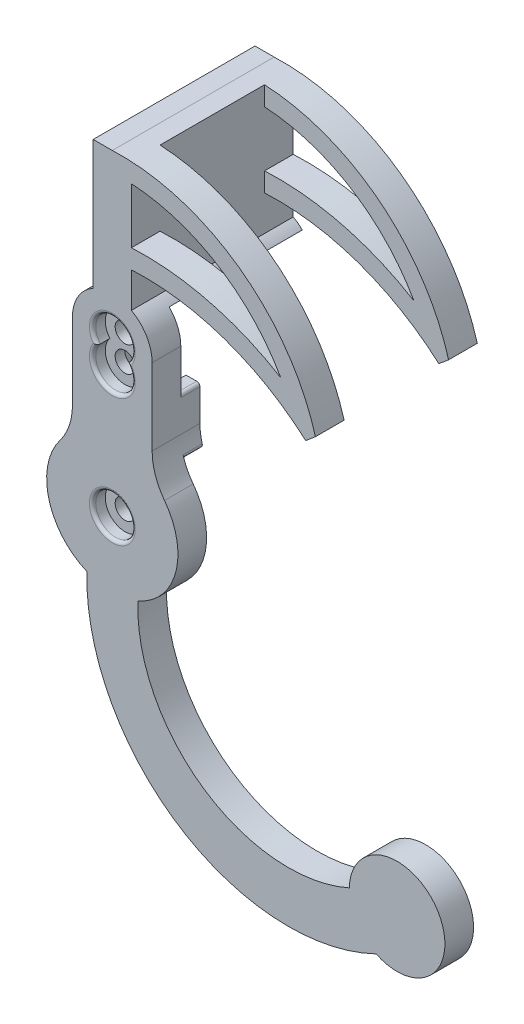
SolidWorks part; units mm, degrees
material "PLA"
ref_plane "Front Plane" through (0, 0, 0) normal (0, 0, 1) x (1, 0, 0)
ref_plane "Top Plane" through (0, 0, 0) normal (0, 1, 0) x (1, 0, 0)
ref_plane "Right Plane" through (0, 0, 0) normal (1, 0, 0) x (0, 0, -1)
sketch "Sketch1" plane through (0, 0, 0) normal (0, 0, 1) x (1, 0, 0)
  line L0 (-15.8075, -15.8075) -> (15.8075, 15.8075) construction
  line L1 (-15.8075, 15.8075) -> (15.8075, -15.8075) construction
  line L2 (0, 0) -> (0, 22.3552) construction
  line L3 (-3.5028, 12) -> (-3.35, 24)
  line L4 (-6.2528, 12) -> (-6.2528, 24)
  line L5 (6.2528, 12) -> (6.2528, 24)
  line L6 (3.5028, 12) -> (3.35, 24)
  line L9 (0.65, -3.8962) -> (0.65, -7.1706)
  line L10 (3.15, 12) -> (3.15, 24)
  line L11 (-3.15, 24) -> (-3.15, 12)
  line L12 (-0.65, -7.1706) -> (-0.65, -3.8962)
  line L13 (-0.65, 3.8962) -> (-0.65, 7.6481)
  line L14 (0.65, 7.6481) -> (0.65, 3.8962)
  line L15 (0.65, -3.8962) -> (0.65, -7.1706) construction
  line L16 (3.15, 12) -> (3.15, 24) construction
  line L17 (-3.15, 24) -> (-3.15, 12) construction
  line L18 (-0.65, -7.1706) -> (-0.65, -3.8962) construction
  line L19 (-0.65, 3.8962) -> (-0.65, 7.6481) construction
  line L20 (0.65, 7.6481) -> (0.65, 3.8962) construction
  circle A0 centre (0, 0) radius 22.3552 construction
  circle A1 centre (0, 20) radius 1.55
  circle A2 centre (0, 24) radius 1.55
  arc A3 (0.7949, 10.2721) -> (-0.7949, 10.2721) centre (0, 0) ccw
  circle A4 centre (-15.7528, 12) radius 12.25 construction
  arc A5 (-3.7402, 9.5999) -> (-3.5028, 12) centre (-15.7528, 12) ccw
  arc A6 (3.35, 24) -> (-3.35, 24) centre (0, 24) ccw
  circle A7 centre (-15.7528, 12) radius 9.5 construction
  arc A9 (-6.2528, 12) -> (-8.1957, 6.2432) centre (-15.7528, 12) cw
  arc A11 (-6.2528, 24) -> (6.2528, 24) centre (0, 24) cw
  arc A12 (0.65, -7.1706) -> (5.7275, 4.363) centre (0, 0) ccw
  arc A13 (3.15, 12) -> (5.7275, 4.363) centre (15.7528, 12) ccw
  arc A14 (3.15, 24) -> (-3.15, 24) centre (0, 24) ccw
  arc A15 (-5.7275, 4.363) -> (-3.15, 12) centre (-15.7528, 12) ccw
  arc A16 (-5.7275, 4.363) -> (-0.65, -7.1706) centre (0, 0) ccw
  arc A17 (-0.65, 3.8962) -> (-0.65, -3.8962) centre (0, 0) ccw
  arc A18 (0.65, 7.6481) -> (-0.65, 7.6481) centre (0, 9) ccw
  arc A19 (0.65, -3.8962) -> (0.65, 3.8962) centre (0, 0) ccw
  arc A20 (0.65, -7.1706) -> (5.7275, 4.363) centre (0, 0) ccw construction
  arc A21 (3.15, 12) -> (5.7275, 4.363) centre (15.7528, 12) ccw construction
  arc A22 (3.15, 24) -> (-3.15, 24) centre (0, 24) ccw construction
  arc A23 (-5.7275, 4.363) -> (-3.15, 12) centre (-15.7528, 12) ccw construction
  arc A24 (-5.7275, 4.363) -> (-0.65, -7.1706) centre (0, 0) ccw construction
  arc A25 (-0.65, 3.8962) -> (-0.65, -3.8962) centre (0, 0) ccw construction
  arc A26 (0.65, 7.6481) -> (-0.65, 7.6481) centre (0, 9) ccw construction
  arc A27 (0.65, -3.8962) -> (0.65, 3.8962) centre (0, 0) ccw construction
  arc A29 (-8.1957, 6.2432) -> (8.1957, 6.2432) centre (0, 0) ccw
  circle A30 centre (0, 0) radius 7.7902
  arc A31 (-3.7402, 9.5999) -> (-5.1734, 5.8243) centre (22.9017, -2.673) ccw
  arc A32 (3.7402, 9.5999) -> (5.1734, 5.8243) centre (-22.9017, -2.673) cw
  arc A33 (3.7402, 9.5999) -> (3.5028, 12) centre (15.7528, 12) cw
  arc A34 (6.2528, 12) -> (8.1957, 6.2432) centre (15.7528, 12) ccw
  dimension "D1" = 3.1
  dimension "D2" = 3.1
  dimension "D6" = 19
  dimension "D8" = 24.5
  dimension "D9" = 15.5803
  dimension "D3" = 4
  dimension "D4" = 20
  dimension "D5" = 45
  dimension "D7" = 0
extrude "Boss-Extrude1" add sketch "Sketch1" along normal blind 3.5 contours A2 | A1 | A9 A29 A34 L5 A11 L4 region at (0, 20, 0) region at (0, 24, 0)
extrude "Boss-Extrude2" add sketch "Sketch1<6>" against normal blind 1 contours A9 A29 A34 L5 A11 L4 A33 A32 A30 A31 A5 L3 A6 L6 region at (-5.7979, 18, 0)
sketch "Sketch1<6>" plane through (0, 0, 0) normal (0, 0, 1) x (1, 0, 0) same geometry as "Sketch1"
sketch "Sketch2" plane through (0, 0, -1) normal (0, 0, -1) x (-1, 0, 0)
  line L0 (3.5832, 17.4665) -> (3.6529, 11.9938)
  line L1 (0, 0) -> (0, 24) construction
  line L2 (6.2528, 12) -> (6.2528, 24)
  line L3 (-6.2528, 24) -> (-6.2528, 12)
  line L4 (6.2528, 12) -> (6.2528, 24)
  line L5 (-6.2528, 24) -> (-6.2528, 12)
  line L6 (3.5028, 12) -> (3.35, 24)
  line L7 (-3.35, 24) -> (-3.5028, 12)
  line L8 (3.5028, 12) -> (3.35, 24) construction
  line L9 (-3.35, 24) -> (-3.5028, 12) construction
  line L10 (6.2528, 17.5004) -> (3.5832, 17.4665)
  line L11 (4.2882, 8.1307) -> (6.7516, 8.9621)
  line L12 (-3.5832, 17.4665) -> (-3.6529, 11.9938)
  line L13 (-6.2528, 17.5004) -> (-3.5832, 17.4665)
  line L14 (-4.2882, 8.1307) -> (-6.7516, 8.9621)
  circle A0 centre (15.7528, 12) radius 12.0999 construction
  arc A1 (4.2882, 8.1307) -> (3.6529, 11.9938) centre (15.7528, 12) cw
  arc A2 (-4.2882, 8.1307) -> (-3.6529, 11.9938) centre (-15.7528, 12) ccw
  arc A4 (6.2528, 12) -> (8.1957, 6.2432) centre (15.7528, 12) ccw
  arc A5 (6.2528, 24) -> (-6.2528, 24) centre (0, 24) ccw
  arc A6 (-8.1957, 6.2432) -> (-6.2528, 12) centre (-15.7528, 12) ccw
  arc A7 (-8.1957, 6.2432) -> (8.1957, 6.2432) centre (0, 0) ccw
  arc A8 (6.2528, 12) -> (8.1957, 6.2432) centre (15.7528, 12) ccw
  arc A9 (6.2528, 24) -> (-6.2528, 24) centre (0, 24) ccw
  arc A10 (-8.1957, 6.2432) -> (-6.2528, 12) centre (-15.7528, 12) ccw
  arc A11 (-8.1957, 6.2432) -> (8.1957, 6.2432) centre (0, 0) ccw
  arc A14 (-3.7402, 9.5999) -> (-3.5028, 12) centre (-15.7528, 12) ccw
  arc A15 (-3.7402, 9.5999) -> (-5.1734, 5.8243) centre (22.9017, -2.673) ccw
  arc A16 (-5.1734, 5.8243) -> (5.1734, 5.8243) centre (0, 0) ccw
  arc A17 (5.1734, 5.8243) -> (3.7402, 9.5999) centre (-22.9017, -2.673) ccw
  arc A18 (3.5028, 12) -> (3.7402, 9.5999) centre (15.7528, 12) ccw
  arc A19 (3.35, 24) -> (-3.35, 24) centre (0, 24) ccw
  arc A20 (-3.7402, 9.5999) -> (-3.5028, 12) centre (-15.7528, 12) ccw construction
  arc A21 (-3.7402, 9.5999) -> (-5.1734, 5.8243) centre (22.9017, -2.673) ccw construction
  arc A22 (-5.1734, 5.8243) -> (5.1734, 5.8243) centre (0, 0) ccw construction
  arc A23 (5.1734, 5.8243) -> (3.7402, 9.5999) centre (-22.9017, -2.673) ccw construction
  arc A24 (3.5028, 12) -> (3.7402, 9.5999) centre (15.7528, 12) ccw construction
  arc A25 (3.35, 24) -> (-3.35, 24) centre (0, 24) ccw construction
  arc M20 (8.1957, 6.2432) -> (6.2528, 12) centre (15.7528, 12) cw
  line M21 (6.2528, 12) -> (6.2528, 24)
  arc M24 (-6.2528, 12) -> (-8.1957, 6.2432) centre (-15.7528, 12) cw
  dimension "D3" = 0.15
  dimension "D4" = 5.5
  dimension "D1" = 0
  dimension "D2" = 0
extrude "Boss-Extrude3" add sketch "Sketch2" along normal blind 3 contours A1 L11 L10 L0 M20 M21 | L14 A2 L12 L13 L5 M24 region at (-4.9977, 13.015, -1) region at (4.9977, 13.015, -1)
sketch "Sketch3" plane through (0, 0, 3.5) normal (0, 0, 1) x (1, 0, 0)
  circle A0 centre (0, 24) radius 1.55 construction
  circle A1 centre (0, 20) radius 1.55 construction
  circle A2 centre (0, 24) radius 1.55
  circle A3 centre (0, 20) radius 1.55
  circle A4 centre (0, 20) radius 3.1
  circle A5 centre (0, 24) radius 3.1
  dimension "D1" = 6.2
  dimension "D2" = 6.2
extrude "Cut-Extrude1" cut sketch "Sketch3" against normal blind 2
sketch "Sketch8" plane through (0, 0, 0) normal (0, 0, -1) x (-1, 0, 0)
  line L0 (3.75, 24) -> (4.4574, 9)
  line L1 (4.4574, 9) -> (7.2239, 3.9848)
  line L2 (0, 24) -> (0, 0) construction
  line L3 (-4.4574, 9) -> (-7.2239, 3.9848)
  line L4 (-3.75, 24) -> (-4.4574, 9)
  circle A0 centre (0, 0) radius 8.25
  circle A1 centre (0, 24) radius 3.75
  arc M7 (-3.5028, 12) -> (-3.7402, 9.5999) centre (-15.7528, 12) cw
  arc M8 (-3.7402, 9.5999) -> (-5.1734, 5.8243) centre (22.9017, -2.673) ccw
  arc M9 (-5.1734, 5.8243) -> (5.1734, 5.8243) centre (0, 0) ccw
  arc M10 (5.1734, 5.8243) -> (3.7402, 9.5999) centre (-22.9017, -2.673) ccw
  arc M11 (3.7402, 9.5999) -> (3.5028, 12) centre (15.7528, 12) cw
  line M12 (3.5028, 12) -> (3.35, 24)
  arc M13 (3.35, 24) -> (-3.35, 24) centre (0, 24) ccw
  line M14 (-3.35, 24) -> (-3.5028, 12)
  circle M15 centre (0, 24) radius 1.55
  circle M16 centre (0, 20) radius 1.55
  dimension "D1" = 7.5
  dimension "D2" = 16.5
  dimension "D3" = 2.7
  dimension "D4" = 15
extrude "Cut-Extrude7" cut sketch "Sketch8" along normal blind 11 contours A1 M15 M16 M12 M13 M14 | L2 A0 A1 M16 M10 M11 M12 | A0 M10 M8 M9 | L2 A1 A0 M16 M14 M7 M8 | A1 L4 L3 A0 M8 M7 M14 | A0 M10 M9 M8 | A1 A0 L1 L0 M12 M11 M10 | A1 M14 M13 M12 region at (-3.564, 23.1777, 0) region at (-4.0843, 13.7832, 0) region at (4.0843, 13.7832, 0) region at (-1.9538, 13.8224, 0) region at (-2.5106, 21.3449, 0) region at (-7.7742, 2.002, 0) region at (1.9538, 13.8224, 0) region at (-4.836, 6.1568, 0)
ref_plane "Plane1" through (0, 0, 4.5) normal (0, 0, 1) x (1, 0, 0)
sketch "Sketch4" plane through (0, 0, 3.5) normal (0, 0, 1) x (1, 0, 0)
  line L0 (0, 0) -> (34.7263, 0) construction
  line L1 (0, 0) -> (25.4725, -30.357) construction
  line L2 (25.4725, -30.357) -> (26.7581, -31.8891)
  line L3 (34.7263, 0) -> (49.7263, 0)
  line L4 (35, -3) -> (8.4853, -3)
  line L5 (35, 3) -> (8.4853, 3)
  line L6 (35, 3) -> (49.7263, 3)
  line L7 (49.7263, 3) -> (49.7263, 0)
  line L9 (38.0037, -3) -> (46.7056, -3)
  line L10 (-3, 35) -> (-3, 49.7263)
  line L11 (-3, 35) -> (-3, 8.4853)
  line L12 (3, 35) -> (3, 8.4853)
  line L13 (3, 38.0037) -> (3, 46.7056)
  line L14 (30.357, 25.4725) -> (31.8891, 26.7581)
  line L15 (0, 0) -> (-3.3379, -4.9858) construction
  line L16 (0, 0) -> (4.9858, -3.3379) construction
  line L17 (-3, 49.7263) -> (0, 49.7263)
  circle A0 centre (0, 0) radius 9
  arc A3 (34.7263, 0) -> (25.4725, -30.357) centre (-3.3379, -4.9858) cw
  arc A4 (49.7263, 0) -> (26.7581, -31.8891) centre (17.9508, -1.3297) cw
  circle A5 centre (17.9508, -1.3297) radius 31.8032 construction
  arc A6 (49.7263, 0) -> (49.458, 3) centre (17.9508, -1.3297) ccw
  circle A7 centre (17.9508, -1.3297) radius 28.8032 construction
  circle A8 centre (-3.3379, -4.9858) radius 41.3893 construction
  arc A9 (38.0037, -3) -> (32.0548, -26.4435) centre (-3.3379, -4.9858) cw
  arc A10 (46.7056, -3) -> (32.0548, -26.4435) centre (17.9508, -1.3297) cw
  circle A11 centre (0, 0) radius 30.2528 construction
  circle A12 centre (0, 24) radius 6.2528
  circle A13 centre (24, 0) radius 6.2528
  arc A14 (6.2528, 24) -> (-6.2528, 24) centre (0, 24) ccw construction
  arc A15 (0, 34.7263) -> (30.357, 25.4725) centre (4.9858, -3.3379) cw
  arc A16 (3, 38.0037) -> (26.4435, 32.0548) centre (4.9858, -3.3379) cw
  arc A17 (3, 46.7056) -> (26.4435, 32.0548) centre (1.3297, 17.9508) cw
  arc A18 (0, 49.7263) -> (31.8891, 26.7581) centre (1.3297, 17.9508) cw
  point P20 (32.0548, -26.4435)
  arc M23 (6.2528, 24) -> (-6.2528, 24) centre (0, 24) ccw
  dimension "D1" = 18
  dimension "D2" = 35
  dimension "D4" = 6
  dimension "D8" = 18
  dimension "D9" = 3
  dimension "D10" = 3
  dimension "D3" = 2
  dimension "D5" = 15
  dimension "D6" = 50
  dimension "D7" = 3
  dimension "D12" = 90
  dimension "D11" = 2
extrude "Boss-Extrude4" add sketch "Sketch4" against normal up to surface (4.5 mm away) contours A18 L17 L10 L11 L12 A15 L14 L13 A17 A16 M23 region at (-2.5749, 32.243, 3.5) up to face at (0, 3.264, -1)
sketch "Sketch9" plane through (0, 0, 3.5) normal (0, 0, 1) x (1, 0, 0)
  line L0 (36.8359, 36.8061) -> (0, 0) construction
  line L1 (0, 0) -> (44.7057, -32.0375) construction
  line L2 (0, 0) -> (49.25, 24.4835) construction
  line L3 (0, 0) -> (0, -63.249) construction
  circle A0 centre (44.7057, -32.0375) radius 7.5
  circle A1 centre (27.6363, -10.3028) radius 27.6363 construction
  arc A2 (-8.1957, 6.2432) -> (8.1957, 6.2432) centre (0, 0) ccw construction
  arc A3 (4.014, -9.4887) -> (37.2067, -31.9148) centre (27.6363, -10.3028) ccw
  arc A4 (-3.9898, -9.4989) -> (41.4189, -38.779) centre (27.6363, -10.3028) ccw
  circle A5 centre (0, 0) radius 10.3028
  point P8 (0, -10.3028)
  arc M11 (-8.1957, 6.2432) -> (8.1957, 6.2432) centre (0, 0) ccw
  dimension "D2" = 4
  dimension "D3" = 4
  dimension "D4" = 15
  dimension "D1" = 55
extrude "Boss-Extrude5" add sketch "Sketch9" against normal up to surface (4.5 mm away) contours A0 | A4 A0 A3 M11 region at (44.7057, -32.0375, 3.5) region at (37.8375, -36.2522, 3.5) up to face at (0, 3.264, -1)
sketch "Sketch6" plane through (0, 0, 3.5) normal (0, 0, 1) x (1, 0, 0)
  line L1 (7.8026, 12.6303) -> (57.0764, 12.6303)
  line L2 (7.8026, 12.6303) -> (7.8026, -35)
  line L3 (7.8026, -35) -> (57.0764, -35)
  line L4 (57.0764, 12.6303) -> (57.0764, -35)
  line L10 (3, 29.4861) -> (3, 35)
  line L11 (3, 29.4861) -> (3, 35)
  line L12 (30.357, 25.4725) -> (31.8891, 26.7581)
  line L13 (30.357, 25.4725) -> (31.8891, 26.7581)
  line L14 (-6.2528, 24) -> (-6.2528, 12)
  line L15 (0, 49.7263) -> (-3, 49.7263)
  line L16 (0, 49.7263) -> (-3, 49.7263)
  line L17 (-3, 49.7263) -> (-3, 29.4861)
  line L18 (-3, 49.7263) -> (-3, 29.4861)
  line L21 (6.2528, 12) -> (6.2528, 24)
  line L26 (-6.2528, 24) -> (-6.2528, 12)
  line L33 (6.2528, 12) -> (6.2528, 24)
  circle A0 centre (0, 0) radius 10.3028
  arc A8 (6.2528, 24) -> (3, 29.4861) centre (0, 24) ccw
  arc A9 (6.2528, 24) -> (3, 29.4861) centre (0, 24) ccw
  arc A10 (30.357, 25.4725) -> (3, 35) centre (4.9858, -3.3379) ccw
  arc A11 (30.357, 25.4725) -> (3, 35) centre (4.9858, -3.3379) ccw
  arc A12 (31.8891, 26.7581) -> (0, 49.7263) centre (1.3297, 17.9508) ccw
  arc A13 (31.8891, 26.7581) -> (0, 49.7263) centre (1.3297, 17.9508) ccw
  arc A18 (-3, 29.4861) -> (-6.2528, 24) centre (0, 24) ccw
  arc A19 (-8.1957, 6.2432) -> (-6.2528, 12) centre (-15.7528, 12) ccw
  arc A20 (-8.1957, 6.2432) -> (-3.9898, -9.4989) centre (0, 0) ccw
  arc A21 (4.014, -9.4887) -> (8.1957, 6.2432) centre (0, 0) ccw
  arc A22 (4.014, -9.4887) -> (8.1957, 6.2432) centre (0, 0) ccw
  arc A23 (-3.9898, -9.4989) -> (41.4189, -38.779) centre (27.6363, -10.3028) ccw
  arc A24 (-3.9898, -9.4989) -> (41.4189, -38.779) centre (27.6363, -10.3028) ccw
  arc A25 (41.4189, -38.779) -> (37.2067, -31.9148) centre (44.7057, -32.0375) ccw
  arc A26 (41.4189, -38.779) -> (37.2067, -31.9148) centre (44.7057, -32.0375) ccw
  arc A27 (6.2528, 12) -> (8.1957, 6.2432) centre (15.7528, 12) ccw
  arc A28 (4.014, -9.4887) -> (37.2067, -31.9148) centre (27.6363, -10.3028) ccw
  arc A29 (4.014, -9.4887) -> (37.2067, -31.9148) centre (27.6363, -10.3028) ccw
  arc A33 (-3, 29.4861) -> (-6.2528, 24) centre (0, 24) ccw
  arc A34 (-8.1957, 6.2432) -> (-6.2528, 12) centre (-15.7528, 12) ccw
  arc A35 (-8.1957, 6.2432) -> (-3.9898, -9.4989) centre (0, 0) ccw
  arc A42 (6.2528, 12) -> (8.1957, 6.2432) centre (15.7528, 12) ccw
  dimension "D1" = 0
sketch "Sketch11" plane through (0, 0, -1) normal (0, 0, -1) x (-1, 0, 0)
  line L0 (-3, 46.7056) -> (-3, 38.0037) construction
  line L1 (-3, 46.7056) -> (-3, 38.0037)
  line L2 (-4.4214, 28.4214) -> (-2.6517, 26.6517)
  line L3 (2.6517, 26.6517) -> (4.4214, 28.4214)
  line L4 (0, 27.75) -> (0, 52.0657) construction
  line L10 (3.75, 24) -> (4.0578, 17.4725)
  line L11 (4.0578, 17.4725) -> (6.2528, 17.5004)
  line L12 (6.2528, 17.5004) -> (6.2528, 24)
  line L13 (3, 29.4861) -> (3, 49.7263)
  line L14 (3, 49.7263) -> (0, 49.7263)
  line L15 (-31.8891, 26.7581) -> (-30.357, 25.4725)
  line L16 (-3, 35) -> (-3, 29.4861)
  line L17 (-6.2528, 24) -> (-6.2528, 17.5004)
  line L18 (-6.2528, 17.5004) -> (-4.0578, 17.4725)
  line L19 (-4.0578, 17.4725) -> (-3.75, 24)
  line L23 (3, 29.4861) -> (3, 49.7263)
  line L24 (3, 49.7263) -> (0, 49.7263)
  line L25 (-31.8891, 26.7581) -> (-30.357, 25.4725)
  line L26 (-3, 35) -> (-3, 29.4861)
  arc A0 (-3, 38.0037) -> (-26.4435, 32.0548) centre (-4.9858, -3.3379) ccw construction
  arc A1 (-3, 46.7056) -> (-26.4435, 32.0548) centre (-1.3297, 17.9508) ccw construction
  arc A2 (-3, 38.0037) -> (-26.4435, 32.0548) centre (-4.9858, -3.3379) ccw
  arc A3 (-3, 46.7056) -> (-26.4435, 32.0548) centre (-1.3297, 17.9508) ccw
  arc A7 (3.75, 24) -> (-3.75, 24) centre (0, 24) ccw
  arc A9 (6.2528, 24) -> (3, 29.4861) centre (0, 24) ccw
  arc A10 (0, 49.7263) -> (-31.8891, 26.7581) centre (-1.3297, 17.9508) ccw
  arc A11 (-3, 35) -> (-30.357, 25.4725) centre (-4.9858, -3.3379) ccw
  arc A12 (-3, 29.4861) -> (-6.2528, 24) centre (0, 24) ccw
  arc A14 (2.6517, 26.6517) -> (-2.6517, 26.6517) centre (0, 24) ccw
  arc A16 (4.4214, 28.4214) -> (3, 29.4861) centre (0, 24) ccw
  arc A17 (0, 49.7263) -> (-31.8891, 26.7581) centre (-1.3297, 17.9508) ccw
  arc A18 (-3, 35) -> (-30.357, 25.4725) centre (-4.9858, -3.3379) ccw
  arc A19 (-3, 29.4861) -> (-4.4214, 28.4214) centre (0, 24) ccw
  arc M24 (-3.75, 24) -> (3.75, 24) centre (0, 24) cw
  arc M29 (6.2528, 24) -> (3, 29.4861) centre (0, 24) ccw
  line M30 (3, 29.4861) -> (3, 49.7263)
  line M31 (3, 49.7263) -> (0, 49.7263)
  arc M32 (0, 49.7263) -> (-31.8891, 26.7581) centre (-1.3297, 17.9508) ccw
  line M33 (-31.8891, 26.7581) -> (-30.357, 25.4725)
  arc M34 (-30.357, 25.4725) -> (-3, 35) centre (-4.9858, -3.3379) cw
  line M35 (-3, 35) -> (-3, 29.4861)
  arc M36 (-3, 29.4861) -> (-6.2528, 24) centre (0, 24) ccw
  line M41 (-3, 46.7056) -> (-3, 38.0037)
  arc M42 (-3, 38.0037) -> (-26.4435, 32.0548) centre (-4.9858, -3.3379) ccw
  arc M43 (-26.4435, 32.0548) -> (-3, 46.7056) centre (-1.3297, 17.9508) cw
  dimension "D2" = 45
  dimension "D1" = 0
extrude "Boss-Extrude6" add sketch "Sketch11" along normal blind 20.9 contours L4 A14 L3 M29 M30 M31 | L4 L2 M24 M32 M33 M34 M35 M36 M43 M41 M42 region at (3.5084, 28.6837, -1) region at (-1.5658, 38.2584, -1)
ref_plane "Plane2" through (0, 0, -17.4) normal (0, 0, -1) x (-1, 0, 0)
sketch "Sketch12" plane through (0, 0, -17.4) normal (0, 0, -1) x (-1, 0, 0)
  line L0 (-3, 49.7102) -> (-3, 35)
  line L6 (3, 49.7263) -> (0, 49.7263)
  line L7 (-31.8891, 26.7581) -> (-30.357, 25.4725)
  line L8 (-3, 35) -> (-3, 29.4861)
  line L9 (-4.4214, 28.4214) -> (-2.6517, 26.6517)
  line L10 (2.6517, 26.6517) -> (4.4214, 28.4214)
  line L11 (3, 29.4861) -> (3, 49.7263)
  line L13 (-31.8891, 26.7581) -> (-30.357, 25.4725)
  arc A5 (0, 49.7263) -> (-31.8891, 26.7581) centre (-1.3297, 17.9508) ccw
  arc A6 (-3, 35) -> (-30.357, 25.4725) centre (-4.9858, -3.3379) ccw
  arc A7 (-3, 29.4861) -> (-4.4214, 28.4214) centre (0, 24) ccw
  arc A8 (2.6517, 26.6517) -> (-2.6517, 26.6517) centre (0, 24) ccw
  arc A9 (4.4214, 28.4214) -> (3, 29.4861) centre (0, 24) ccw
  arc A10 (-3, 49.7102) -> (-31.8891, 26.7581) centre (-1.3297, 17.9508) ccw
  arc A11 (-3, 35) -> (-30.357, 25.4725) centre (-4.9858, -3.3379) ccw
  dimension "D1" = 0
extrude "Cut-Extrude8" cut sketch "Sketch12" against normal up to surface (16.4 mm away) up to face at (-4.6816, 23.0562, -1)
sketch "Sketch13" plane through (0, 0, 3.5) normal (0, 0, 1) x (1, 0, 0)
  circle A0 centre (0, 0) radius 1.55
  dimension "D1" = 3.1
extrude "Cut-Extrude9" cut sketch "Sketch13" against normal blind 10
sketch "Sketch14" plane through (0, 0, 3.5) normal (0, 0, 1) x (1, 0, 0)
  circle A0 centre (0, 0) radius 3.1
  dimension "D1" = 6.2
extrude "Cut-Extrude10" cut sketch "Sketch14" against normal blind 2 contours A0
fillet "Fillet2" radius 0.5 7 edges at (-6.2528, 17.5004, -2.5) (-6.7516, 8.9621, -2.5) (6.2528, 17.5004, -2.5) (6.7516, 8.9621, -2.5) (0, 27.1, 3.5) (0, 16.9, 3.5) (3.1, 0, 3.5)
equation "\"O_R\"= 4'Outer radius (Addendum)"
equation "\"I_R\"= 2.9'Inner radius (Dedendum)"
equation "\"N\"= 25'# of teeth"
equation "\"phi\"= 20'Pressure angle"
equation "\"P_R\"= 3'Pitch radius"
equation "\"a\"= ( \"period\" - ( \"err\" + \"T_F\" ) * ( \"I_R\" ) ) / ( 1 + ( \"O_R\" / \"I_R\" ) )'Outer arc degree"
equation "\"a_i\"= \"a\" * \"O_R\" / \"I_R\"'Inner arc degree (+manufacturing)"
equation "\"err\"= .03'Manufacturing error"
equation "\"period\"= 360 / \"N\"'Period of gear teeth"
equation "\"T_F\"= \"O_R\" / 2cm'Transition factor for curve"
equation "\"D4@Sketch19\"= \"a_i\" / 2"
